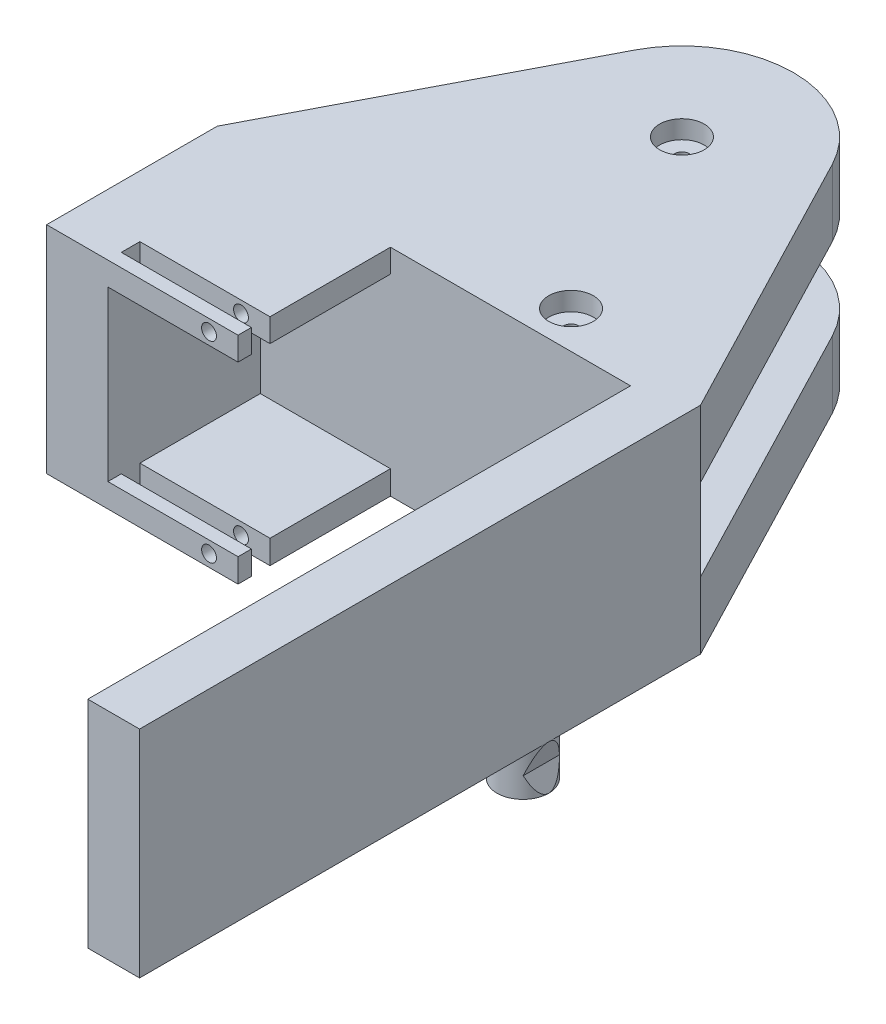
SolidWorks part; units mm, degrees
material "Copper"
ref_plane "Front Plane" through (0, 0, 0) normal (0, 0, 1) x (1, 0, 0)
ref_plane "Top Plane" through (0, 0, 0) normal (0, 1, 0) x (1, 0, 0)
ref_plane "Right Plane" through (0, 0, 0) normal (1, 0, 0) x (0, 0, -1)
sketch "Sketch1" plane through (0, 0, 0) normal (0, 0, 1) x (1, 0, 0)
  line L0 (0, 11) -> (65, 11)
  line L1 (0, 0) -> (65, 0)
  line L2 (0, 0) -> (0, 65)
  line L3 (0, 65) -> (65, 65)
  line L4 (65, 0) -> (65, 65)
  line L5 (0, 0) -> (65, 0)
  line L6 (0, 0) -> (0, 10)
  line L7 (0, 10) -> (65, 10)
  line L8 (65, 0) -> (65, 10)
  line L9 (0, 10) -> (65, 10)
  line L10 (0, 10) -> (0, 20)
  line L11 (0, 20) -> (65, 20)
  line L12 (65, 10) -> (65, 20)
  line L13 (65, 20) -> (0, 20)
  line L14 (65, 20) -> (65, 30)
  line L15 (65, 30) -> (0, 30)
  line L16 (0, 20) -> (0, 30)
  line L17 (0, 30) -> (65, 30)
  line L18 (0, 30) -> (0, 40)
  line L19 (0, 40) -> (65, 40)
  line L20 (65, 30) -> (65, 40)
  line L21 (0, 31) -> (65, 31)
  line L22 (36.97, 30) -> (36.97, 31) construction
  line L23 (37.8533, 10) -> (37.8533, 11) construction
  dimension "D1" = 65
  dimension "D2" = 65
  dimension "D3" = 10
  dimension "D4" = 1
extrude "Boss-Extrude1" add sketch "Sketch1" along normal blind 45 contours L11 L2 L7 L4 | L19 L2 L15 L4 region at (32.5, 15.5, 0) region at (32.5, 35.5, 0)
sketch "Sketch2" plane through (0, 10, 0) normal (0, -1, 0) x (1, 0, 0)
  line L0 (32.5, 0) -> (32.5, 45) construction
  line L3 (0, 45) -> (19.1907, 8.0816)
  line L4 (65, 45) -> (45.8093, 8.0816)
  line L5 (0, 45) -> (0, 0)
  line L6 (0, 0) -> (65, 0)
  line L7 (65, 0) -> (65, 45)
  circle A0 centre (32.5, 15) radius 15
  circle A1 centre (32.5, 15) radius 1
  dimension "D1" = 30
  dimension "D2" = 2
extrude "Cut-Extrude5" cut sketch "Sketch2" against normal blind 34 contours A0 L6 L4 | L0 A1 | A1 L0 | A1 region at (56.7767, 10, 14.6593) region at (32.0756, 10, 15) region at (32.9244, 10, 15)
extrude "Cut-Extrude6" cut sketch "Sketch2<6>" against normal blind 34 contours A0 L3 region at (8.2233, 10, 14.6593)
sketch "Sketch2<6>" plane through (0, 10, 0) normal (0, -1, 0) x (1, 0, 0) same geometry as "Sketch2"
sketch "Sketch3" plane through (0, 40, 0) normal (0, 1, 0) x (1, 0, 0)
  circle A0 centre (32.5, -15) radius 3
  dimension "D1" = 6
extrude "Cut-Extrude7" cut sketch "Sketch3" against normal blind 2.45
sketch "Sketch4" plane through (0, 20, 0) normal (0, 1, 0) x (1, 0, 0)
  circle A0 centre (32.5, -15) radius 3
extrude "Cut-Extrude8" cut sketch "Sketch4" against normal blind 2.45
sketch "Sketch5" plane through (0, 0, 45) normal (0, 0, 1) x (1, 0, 0)
  line L1 (0, 11) -> (65, 11)
  line L2 (0, 11) -> (0, 40)
  line L3 (0, 40) -> (65, 40)
  line L4 (65, 11) -> (65, 40)
extrude "Boss-Extrude2" add sketch "Sketch5" along normal blind 2.45
sketch "Sketch6" plane through (0, 11, 0) normal (0, -1, 0) x (1, 0, 0)
  line L0 (32.5, 15) -> (32.5, 26.7) construction
  line L1 (29, 26.7) -> (36, 26.7)
  line L2 (29, 26.7) -> (29, 33.5539)
  line L3 (29, 33.5539) -> (36, 33.5539)
  line L4 (36, 26.7) -> (36, 33.5539)
  line L5 (32.5, 26.7) -> (32.5, 28.3) construction
  circle A0 centre (32.5, 15) radius 11.5
  circle A1 centre (32.5, 28.3) radius 0.75
  dimension "D1" = 23
  dimension "D2" = 1.5
  dimension "D3" = 7
  dimension "D4" = 1.6
  dimension "D5" = 11.7
extrude "Boss-Extrude3" add sketch "Sketch6" along normal blind 3.35 contours L1 L4 L3 L2 region at (32.5, 11, 30.1968)
sketch "Sketch7" plane through (0, 7.65, 0) normal (0, -1, 0) x (1, 0, 0)
  line L0 (29, 29.7) -> (29, 26.7)
  line L1 (29, 26.7) -> (29, 33.5539) construction
  line L2 (29, 26.7) -> (36, 26.7) construction
  line L3 (29, 26.7) -> (31, 26.7)
  line L4 (31, 26.7) -> (29, 29.7)
  line L5 (34, 26.7) -> (36, 29.7)
  line L6 (36, 26.7) -> (36, 33.5539) construction
  line L7 (36, 29.7) -> (36, 26.7)
  line L8 (36, 26.7) -> (34, 26.7)
  dimension "D1" = 2
  dimension "D2" = 3
extrude "Cut-Extrude9" cut sketch "Sketch7" against normal blind 3.35
sketch "Sketch8" plane through (0, 7.65, 0) normal (0, -1, 0) x (1, 0, 0)
  line L0 (32.5, 33.5539) -> (32.5, 30.1922) construction
  line L1 (29, 33.5539) -> (36, 33.5539) construction
  line L2 (30.4549, 30.3333) -> (30.2789, 27.7817)
  line L3 (31, 26.7) -> (29, 29.7) construction
  line L4 (34.5451, 30.3333) -> (34.7211, 27.7817)
  line L5 (36, 29.7) -> (34, 26.7) construction
  line L7 (29.45, 30.2005) -> (29.4468, 29.0297)
  line L8 (35.55, 30.2005) -> (35.5532, 29.0297)
  line L9 (30.2789, 27.7817) -> (31, 26.7) construction
  line L10 (34.7211, 27.7817) -> (34, 26.7) construction
  line L11 (30.2789, 27.7817) -> (29.4468, 29.0297) construction
  line L12 (35.5532, 29.0297) -> (34.7211, 27.7817) construction
  circle A0 centre (32.5, 30.1922) radius 2.05
  circle A1 centre (32.5, 30.1922) radius 3.05
  line M1 (29, 29.7) -> (31, 26.7)
  line M3 (34, 26.7) -> (36, 29.7)
  line M4 (36, 29.7) -> (36, 33.5539)
  line M5 (36, 33.5539) -> (29, 33.5539)
  line M6 (29, 33.5539) -> (29, 29.7)
  dimension "D1" = 4.1
  dimension "D3" = 1
  dimension "D2" = 3.3617
  dimension "D4" = 1.3
  dimension "D5" = 1.5
extrude "Boss-Extrude4" add sketch "Sketch8" along normal blind 2 contours A1 L8 L7 M3 M4 M5 M6 M1 | L4 A1 L2 A0 | A1 L7 L2 M1 | A1 L4 L8 M3 region at (30.2975, 7.65, 29.2123) region at (29.7908, 7.65, 28.7274) region at (29.3651, 7.65, 29.6153) region at (35.2092, 7.65, 28.7274)
sketch "Sketch9" plane through (0, 0, 47.45) normal (0, 0, 1) x (1, 0, 0)
  line L0 (65, 40) -> (0, 40) construction
  line L1 (65, 11) -> (58.0376, 11)
  line L2 (65, 11) -> (65, 40)
  line L3 (65, 40) -> (58.0376, 40)
  line L4 (58.0376, 11) -> (58.0376, 40)
extrude "Boss-Extrude5" add sketch "Sketch9" along normal blind 73
sketch "Sketch10" plane through (0, 11, 0) normal (0, -1, 0) x (1, 0, 0)
  line L0 (45.0376, 42.45) -> (45.0376, 47.45) construction
  line L1 (0, 47.45) -> (58.0376, 47.45) construction
  line L2 (58.0376, 120.45) -> (58.0376, 47.45) construction
  circle A0 centre (45.0376, 42.45) radius 3
  dimension "D1" = 6
  dimension "D2" = 13
  dimension "D3" = 5
extrude "Cut-Extrude10" cut sketch "Sketch10" against normal blind 2.5
sketch "Sketch11" plane through (0, 40, 0) normal (0, 1, 0) x (1, 0, 0)
  line L0 (45.0376, -42.45) -> (45.0376, -47.45) construction
  line L1 (58.0376, -47.45) -> (0, -47.45) construction
  line L2 (58.0376, -120.45) -> (58.0376, -47.45) construction
  circle A0 centre (45.0376, -42.45) radius 3
  dimension "D1" = 6
  dimension "D2" = 5
  dimension "D3" = 13
extrude "Cut-Extrude11" cut sketch "Sketch11" against normal blind 2.5
sketch "Sketch12" plane through (0, 37.5, 0) normal (0, 1, 0) x (1, 0, 0)
  circle A0 centre (45.0376, -42.45) radius 1
  point P3 (45.0376, -42.45)
extrude "Cut-Extrude12" cut sketch "Sketch12" against normal blind 32.5
sketch "Sketch13" plane through (0, 0, 47.45) normal (0, 0, 1) x (1, 0, 0)
  line L0 (0, 11) -> (58.0376, 11) construction
  line L1 (25.7437, 11) -> (0, 11)
  line L2 (25.7437, 11) -> (25.7437, 40)
  line L3 (25.7437, 40) -> (0, 40)
  line L4 (0, 11) -> (0, 40)
extrude "Boss-Extrude6" add sketch "Sketch13" along normal blind 20.5
sketch "Sketch14" plane through (25.7437, 0, 0) normal (1, 0, 0) x (0, 0, -1)
  line L0 (-47.45, 11) -> (-47.45, 40) construction
  line L1 (-47.45, 9.15) -> (-63.65, 9.15)
  line L2 (-47.45, 9.15) -> (-47.45, 41.85)
  line L3 (-47.45, 41.85) -> (-63.65, 41.85)
  line L4 (-63.65, 9.15) -> (-63.65, 41.85)
  line L5 (-63.65, 25.5) -> (-67.95, 25.5) construction
  line L6 (-67.95, 11) -> (-67.95, 40) construction
  dimension "D1" = 16.2
  dimension "D2" = 32.7
extrude "Cut-Extrude13" cut sketch "Sketch14" against normal blind 17.5
sketch "Sketch16" plane through (8.2437, 0, 0) normal (1, 0, 0) x (0, 0, -1)
  line L0 (-47.45, 11) -> (-47.45, 40) construction
  line L1 (-63.65, 11) -> (-47.45, 11)
  line L2 (-63.65, 11) -> (-63.65, 14.1979)
  line L3 (-63.65, 14.1979) -> (-47.45, 14.1979)
  line L4 (-47.45, 11) -> (-47.45, 14.1979)
  line L5 (-63.65, 40) -> (-47.45, 40)
  line L6 (-63.65, 40) -> (-63.65, 36.8625)
  line L7 (-63.65, 36.8625) -> (-47.45, 36.8625)
  line L8 (-47.45, 40) -> (-47.45, 36.8625)
extrude "Boss-Extrude7" add sketch "Sketch16" along normal blind 17.5
sketch "Sketch17" plane through (25.7437, 0, 0) normal (1, 0, 0) x (0, 0, -1)
  line L0 (-63.65, 36.8625) -> (-47.45, 36.8625) construction
  line L1 (-67.95, 11) -> (-66.15, 11)
  line L2 (-67.95, 11) -> (-67.95, 14.1979)
  line L3 (-67.95, 14.1979) -> (-66.15, 14.1979)
  line L4 (-66.15, 11) -> (-66.15, 14.1979)
  line L5 (-67.95, 40) -> (-66.15, 40)
  line L6 (-67.95, 40) -> (-67.95, 36.8625)
  line L7 (-67.95, 36.8625) -> (-66.15, 36.8625)
  line L8 (-66.15, 40) -> (-66.15, 36.8625)
  line L9 (-47.45, 14.1979) -> (-63.65, 14.1979) construction
  line L10 (-63.65, 14.1979) -> (-63.65, 36.8625) construction
  line L12 (-67.95, 36.8625) -> (-63.65, 36.8625)
  line L13 (-67.95, 36.8625) -> (-67.95, 14.1979)
  line L14 (-67.95, 14.1979) -> (-63.65, 14.1979)
  line L15 (-63.65, 36.8625) -> (-63.65, 14.1979)
  line L16 (-63.65, 14.1979) -> (-66.15, 14.1979)
  line L17 (-63.65, 14.1979) -> (-63.65, 11)
  line L18 (-63.65, 11) -> (-66.15, 11)
  line L19 (-66.15, 14.1979) -> (-66.15, 11)
  line L20 (-63.65, 36.8625) -> (-66.15, 36.8625)
  line L21 (-63.65, 36.8625) -> (-63.65, 40)
  line L22 (-63.65, 40) -> (-66.15, 40)
  line L23 (-66.15, 36.8625) -> (-66.15, 40)
  line M4 (-67.95, 11) -> (-47.45, 11)
  line M7 (-63.65, 14.1979) -> (-63.65, 36.8625)
  line M10 (-47.45, 40) -> (-67.95, 40)
  line M11 (-67.95, 40) -> (-67.95, 11)
  dimension "D1" = 2.5
extrude "Cut-Extrude14" cut sketch "Sketch17" against normal blind 17.5 contours L3 L14 L12 L7 M7 M11 | L17 L14 L4 M4 | L12 L21 L8 M10 region at (25.7437, 12.5989, 64.9) region at (25.7437, 25.5302, 65.8) region at (25.7437, 38.4312, 64.9)
sketch "Sketch19" plane through (0, 0, 67.95) normal (0, 0, 1) x (1, 0, 0)
  line L1 (8.2437, 36.8625) -> (8.2437, 14.1979) construction
  line L2 (21.8437, 38.4312) -> (25.7437, 38.4312) construction
  line L3 (25.7437, 36.8625) -> (25.7437, 40) construction
  line L4 (21.8437, 12.5989) -> (25.7437, 12.5989) construction
  line L5 (25.7437, 11) -> (25.7437, 14.1979) construction
  circle A0 centre (21.8437, 12.5989) radius 1
  circle A1 centre (21.8437, 38.4312) radius 1
  dimension "D1" = 2
  dimension "D2" = 12.6
  dimension "D3" = 12.6
extrude "Cut-Extrude15" cut sketch "Sketch19" against normal blind 10
sketch "Sketch20" plane through (0, 11, 0) normal (0, -1, 0) x (1, 0, 0)
  line L0 (65, 65.4111) -> (58.0376, 65.4111) construction
  line L1 (65, 120.45) -> (65, 45) construction
  line L2 (58.0376, 120.45) -> (58.0376, 47.45) construction
  circle A0 centre (61.5188, 65.4111) radius 3.4812
extrude "Boss-Extrude8" add sketch "Sketch20" along normal blind 6
sketch "Sketch22" plane through (0, 0, 120.45) normal (0, 0, 1) x (1, 0, 0)
  line L0 (65, 11) -> (65, 40) construction
  line L1 (65, 14.9198) -> (58.0376, 14.9198)
  line L2 (65, 14.9198) -> (65, 5)
  line L3 (65, 5) -> (58.0376, 5)
  line L4 (58.0376, 14.9198) -> (58.0376, 5)
  line L5 (58.0376, 40) -> (58.0376, 11) construction
  line L6 (58.0376, 5) -> (65, 5) construction
  line L7 (65, 5) -> (64, 7.7559)
  line L8 (64, 7.7559) -> (65, 11)
  line L9 (64, 7.7559) -> (65, 7.7559) construction
  dimension "D1" = 1
extrude "Cut-Extrude17" cut sketch "Sketch22" against normal blind 66 contours L8 L9 L2 | L9 L7 L2 region at (64.6667, 8.8372, 120.45) region at (64.6667, 6.8372, 120.45)
